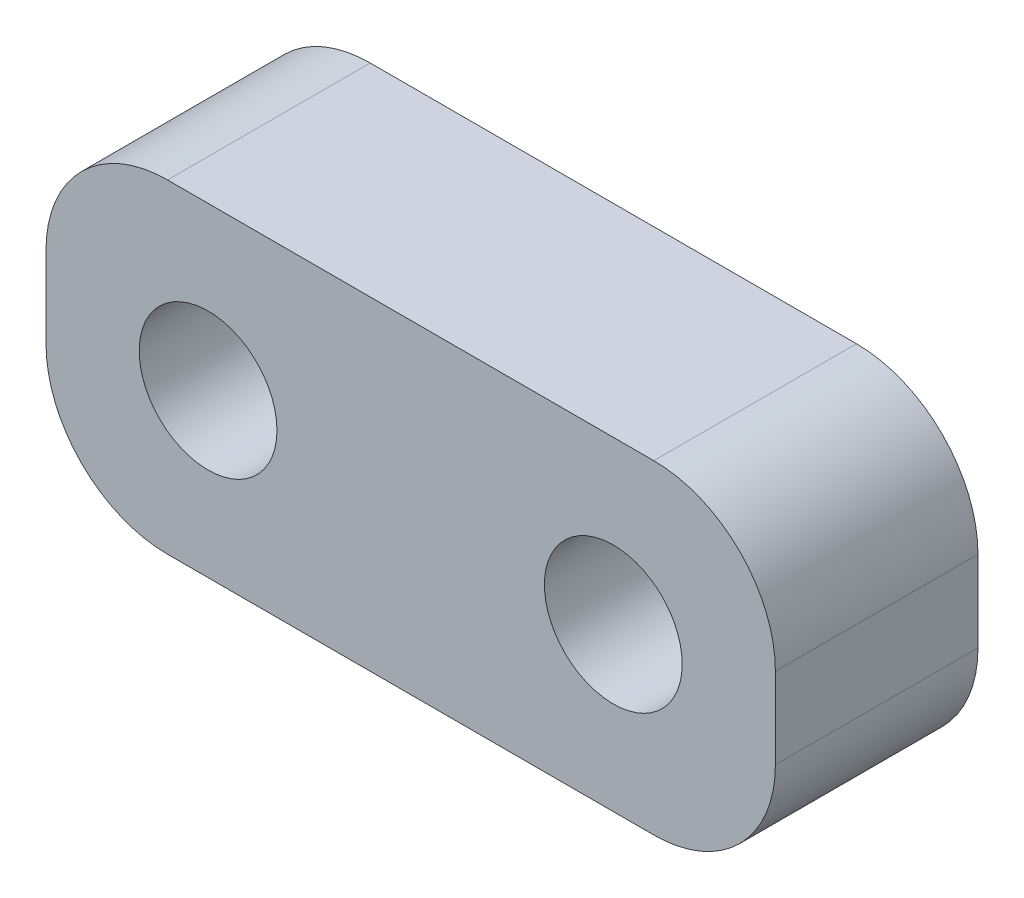
SolidWorks part; units mm, degrees
material "ABS"
ref_plane "Front Plane" through (0, 0, 0) normal (0, 0, 1) x (1, 0, 0)
ref_plane "Top Plane" through (0, 0, 0) normal (0, 1, 0) x (1, 0, 0)
ref_plane "Right Plane" through (0, 0, 0) normal (1, 0, 0) x (0, 0, -1)
ref_axis "X" through (-88.99, 0, 0) along (1, 0, 0)
ref_axis "Y" through (0, 55, 0) along (0, -1, 0)
ref_axis "Z" through (0, 0, -88.99) along (0, 0, 1)
sketch "Sketch1" plane through (0, 0, 0) normal (0, 0, 1) x (1, 0, 0)
  line L0 (-5, 0) -> (5, 0) construction
  line L1 (-9, 4) -> (9, 4)
  line L2 (-9, 4) -> (-9, -4)
  line L3 (-9, -4) -> (9, -4)
  line L4 (9, 4) -> (9, -4)
  line L5 (-9, 4) -> (9, -4) construction
  line L6 (-9, -4) -> (9, 4) construction
  circle A0 centre (-5, 0) radius 1.75 construction
  circle A1 centre (5, 0) radius 1.75 construction
  point P0 (0, 0)
  point P9 (0, 0)
  dimension "D4" = 3.5
  dimension "D1" = 8
  dimension "D2" = 18
  dimension "D3" = 10
extrude "Boss-Extrude1" add sketch "Sketch1" along normal mid plane 5
sketch "Sketch4" plane through (0, 0, 2.5) normal (0, 0, 1) x (1, 0, 0)
  point P0 (-5, 0)
  point P3 (5, 0)
hole_wizard "M3 Clearance Hole1" positions "Sketch4" profile "Sketch3" hole size "M3" standard "ANSI Metric" end condition through all
sketch "Sketch3" plane through (-5, 0, 2.5) normal (1, 0, 0) x (0, -1, 0)
  line L0 (0, 0) -> (0, 5)
  line L1 (0, 5) -> (1.7, 5)
  line L2 (1.7, 5) -> (1.7, 0)
  line L5 (1.7, 0) -> (0, 0)
  line L11 (0, -6.35) -> (0, 107.95) construction
  dimension "Thru Hole Dia." = 3.4
  dimension "Thru Hole Depth" = 5
fillet "Fillet1" radius 3 4 edges at (-9, 4, 0) (-9, -4, 0) (9, -4, 0) (9, 4, 0)
